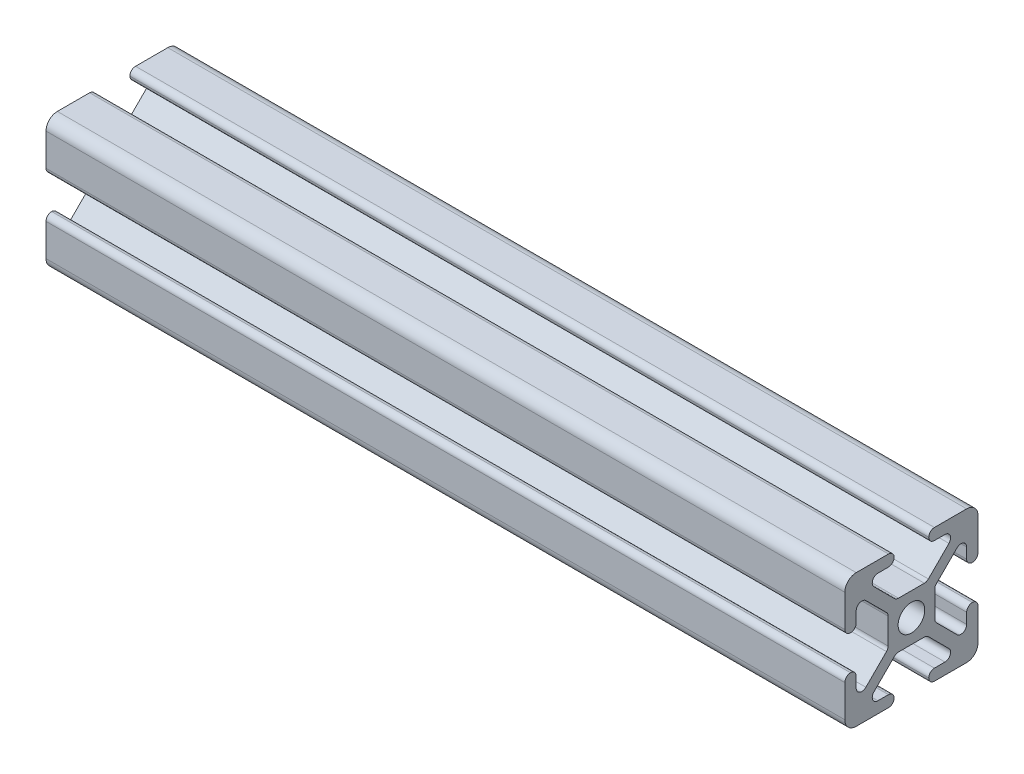
SolidWorks part; units mm, degrees
ref_plane "Front Plane" through (0, 0, 0) normal (1, 0, 0) x (0, 1, 0)
ref_plane "Top Plane" through (0, 0, 0) normal (0, 0, 1) x (0, 1, 0)
ref_plane "Right Plane" through (0, 0, 0) normal (0, 1, 0) x (-1, 0, 0)
sketch "Sketch1" plane through (0, 0, 0) normal (1, 0, 0) x (0, 1, 0)
  line L0 (0, 0) -> (0, 12.5) construction
  line L1 (-12.5, -12.5) -> (12.5, -12.5)
  line L2 (-12.5, -12.5) -> (-12.5, 12.5)
  line L3 (-12.5, 12.5) -> (12.5, 12.5)
  line L4 (12.5, -12.5) -> (12.5, 12.5)
  line L5 (-12.5, -12.5) -> (12.5, 12.5) construction
  line L6 (-12.5, 12.5) -> (12.5, -12.5) construction
  line L7 (-3.25, 12.5) -> (-3.25, 10.37)
  line L8 (-3.25, 10.37) -> (-8.8639, 10.37)
  line L9 (-8.8639, 10.37) -> (-2.8739, 4.38)
  line L10 (-2.8739, 4.38) -> (2.8739, 4.38)
  line L11 (8.8639, 10.37) -> (2.8739, 4.38)
  line L12 (3.25, 10.37) -> (8.8639, 10.37)
  line L13 (3.25, 12.5) -> (3.25, 10.37)
  line L14 (12.5, -3.25) -> (10.37, -3.25)
  line L15 (10.37, -3.25) -> (10.37, -8.8639)
  line L16 (10.37, -8.8639) -> (4.38, -2.8739)
  line L17 (4.38, 2.8739) -> (4.38, -2.8739)
  line L18 (10.37, 8.8639) -> (4.38, 2.8739)
  line L19 (10.37, 3.25) -> (10.37, 8.8639)
  line L20 (12.5, 3.25) -> (10.37, 3.25)
  line L21 (-3.25, -12.5) -> (-3.25, -10.37)
  line L22 (-3.25, -10.37) -> (-8.8639, -10.37)
  line L23 (-8.8639, -10.37) -> (-2.8739, -4.38)
  line L24 (2.8739, -4.38) -> (-2.8739, -4.38)
  line L25 (8.8639, -10.37) -> (2.8739, -4.38)
  line L26 (3.25, -10.37) -> (8.8639, -10.37)
  line L27 (3.25, -12.5) -> (3.25, -10.37)
  line L28 (-12.5, 3.25) -> (-10.37, 3.25)
  line L29 (-10.37, 3.25) -> (-10.37, 8.8639)
  line L30 (-10.37, 8.8639) -> (-4.38, 2.8739)
  line L31 (-4.38, -2.8739) -> (-4.38, 2.8739)
  line L32 (-10.37, -8.8639) -> (-4.38, -2.8739)
  line L33 (-10.37, -3.25) -> (-10.37, -8.8639)
  line L34 (-12.5, -3.25) -> (-10.37, -3.25)
  circle A0 centre (0, 0) radius 2.5
  point P0 (0, 0)
  point P15 (0, 4.38)
  dimension "D3" = 5
  dimension "D1" = 25
  dimension "D2" = 25
  dimension "D4" = 2.13
  dimension "D5" = 2.13
  dimension "D6" = 6.5
  dimension "D7" = 4.38
  dimension "D8" = 4
extrude "Boss-Extrude1" add sketch "Sketch1" along normal blind 150 contours L34 L2 L1 L21 L22 L23 L24 L25 L26 L27 L4 L14 L15 L16 L17 L18 L19 L20 L3 L13 L12 L11 L10 L9 L8 L7 L28 L29 L30 L31 L32 L33 A0 region at (0, -12.1464, -7.875)
fillet "Fillet1" radius 1.065 32 edges at (75, -10.37, -8.8639) (75, 2.8739, -4.38) (75, -2.8739, -4.38) (75, -4.38, 2.8739) (75, -4.38, -2.8739) (75, -2.8739, 4.38) (75, 2.8739, 4.38) (75, 4.38, 2.8739) (75, 4.38, -2.8739) (75, -8.8639, -10.37) (75, 8.8639, -10.37) (75, 10.37, -8.8639) (75, -10.37, 8.8639) (75, -8.8639, 10.37) (75, 10.37, 8.8639) (75, 8.8639, 10.37) (75, 12.5, 3.25) (75, -3.25, -12.5) (75, -10.37, 3.25) (75, 10.37, 3.25) (75, -10.37, -3.25) (75, -12.5, -3.25) (75, -12.5, 3.25) (75, 3.25, -10.37) (75, -3.25, -10.37) (75, 3.25, -12.5) (75, 10.37, -3.25) (75, 12.5, -3.25) (75, 3.25, 12.5) (75, 3.25, 10.37) (75, -3.25, 10.37) (75, -3.25, 12.5)
fillet "Fillet2" radius 2.13 4 edges at (75, 12.5, -12.5) (75, -12.5, -12.5) (75, 12.5, 12.5) (75, -12.5, 12.5)
